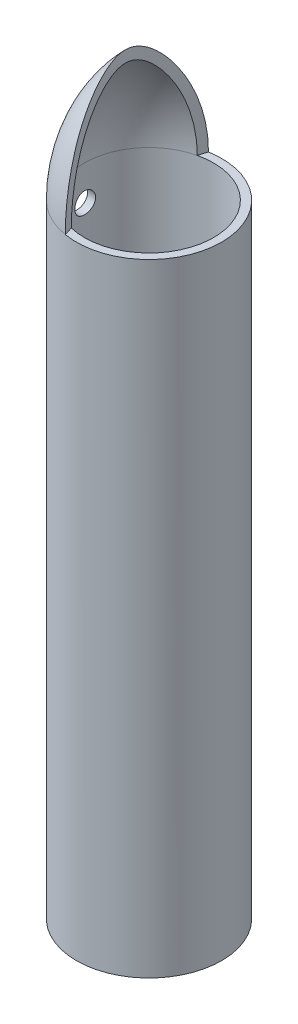
SolidWorks part; units mm, degrees
ref_plane "Front Plane" through (0, 0, 0) normal (0, 0, 1) x (1, 0, 0)
ref_plane "Top Plane" through (0, 0, 0) normal (0, 1, 0) x (1, 0, 0)
ref_plane "Right Plane" through (0, 0, 0) normal (1, 0, 0) x (0, 0, -1)
sketch "Sketch1" plane through (0, 0, 0) normal (0, 1, 0) x (1, 0, 0)
  circle A0 centre (0, 0) radius 9.35
  circle A1 centre (0, 0) radius 10.5
  dimension "D1" = 21
  dimension "D2" = 18.7
extrude "Boss-Extrude1" add sketch "Sketch1" along normal mid plane 90
sketch "Sketch3" plane through (0, 45, 0) normal (0, 1, 0) x (1, 0, 0)
  circle A0 centre (29.75, 0) radius 33.16
  circle A1 centre (0, 0) radius 9.35 construction
  dimension "D1" = 29.75
  dimension "D2" = 66.32
sketch "Sketch2" plane through (0, 0, 0) normal (0, 0, 1) x (1, 0, 0)
  line L0 (0, 65) -> (0, 45) construction
  line L1 (10.5, 45) -> (-10.5, 45) construction
  line L4 (9.35, 45) -> (-9.35, 45) construction
  line L5 (10.5, 45) -> (9.35, 45)
  line L6 (0, 63.586) -> (0, 65)
  arc A0 (10.5, 45) -> (0, 65) centre (-13.7976, 45) ccw
  arc A1 (9.35, 45) -> (0, 63.586) centre (-13.7976, 45) ccw
  point P3 (0, 0)
  dimension "D1" = 20
revolve "Revolve1" add sketch "Sketch2" angle 360 about L0
extrude "Cut-Extrude1" cut sketch "Sketch3" along normal through all contours A0
sketch "Sketch4" plane through (0, 0, 0) normal (1, 0, 0) x (0, 0, -1)
  line L0 (10.5, 45) -> (-10.5, 45) construction
  circle A0 centre (0, 40) radius 1.5
  point P4 (0, 0)
  dimension "D1" = 3
  dimension "D2" = 5
extrude "Cut-Extrude2" cut sketch "Sketch4" against normal through all
